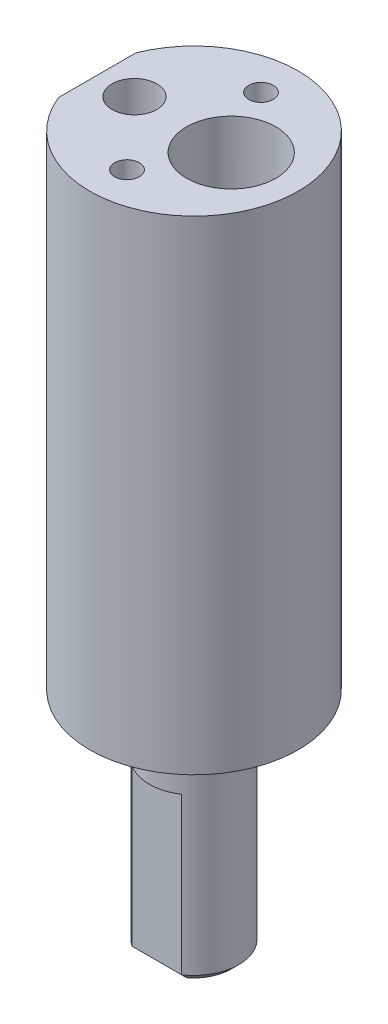
SolidWorks part; units mm, degrees
ref_plane "Front Plane" through (0, 0, 0) normal (0, 0, 1) x (1, 0, 0)
ref_plane "Top Plane" through (0, 0, 0) normal (0, 1, 0) x (1, 0, 0)
ref_plane "Right Plane" through (0, 0, 0) normal (1, 0, 0) x (0, 0, -1)
sketch "Sketch2" plane through (0, 0, 0) normal (0, 1, 0) x (1, 0, 0)
  line L0 (3.3166, -5) -> (-3.3166, -5)
  arc A0 (3.3166, -5) -> (-3.3166, -5) centre (0, 0) ccw
  dimension "D1" = 12
  dimension "D2" = 5
extrude "Boss-Extrude2" add sketch "Sketch2" along normal blind 22 contours A0 L0
sketch "Sketch6" plane through (0, 22, 0) normal (0, 1, 0) x (1, 0, 0)
  circle A0 centre (0, 0) radius 6
  dimension "D1" = 12
extrude "Boss-Extrude3" add sketch "Sketch6" along normal blind 8
sketch "Sketch7" plane through (0, 30, 0) normal (0, 1, 0) x (1, 0, 0)
  line L0 (-13, 5.1962) -> (-13, -5.1962)
  arc A0 (-13, -5.1962) -> (-13, 5.1962) centre (0, 0) ccw
  dimension "D1" = 28
  dimension "D2" = 13
extrude "Boss-Extrude4" add sketch "Sketch7" along normal blind 65
sketch "Sketch8" plane through (0, 95, 0) normal (0, 1, 0) x (1, 0, 0)
  line L0 (0, 0) -> (-13, 0) construction
  line L1 (-13, 5.1962) -> (-13, -5.1962) construction
  circle A0 centre (-8, 0) radius 3
  dimension "D2" = 6
  dimension "D1" = 8
extrude "Cut-Extrude5" cut sketch "Sketch8" against normal blind 65 contours A0
sketch "Sketch9" plane through (0, 95, 0) normal (0, 1, 0) x (1, 0, 0)
  circle A0 centre (5, 0) radius 6
  dimension "D2" = 12
  dimension "D1" = 5
extrude "Cut-Extrude6" cut sketch "Sketch9" against normal blind 52 contours A0
sketch "Sketch11" plane through (0, 95, 0) normal (0, 1, 0) x (1, 0, 0)
  line L0 (0, 14) -> (0, -14) construction
  arc A0 (-13, -5.1962) -> (-13, 5.1962) centre (0, 0) ccw construction
  point P6 (0, 9)
  point P7 (0, -9)
  point P8 (0, 9)
  dimension "D1" = 9
  dimension "D2" = 9
hole_wizard "M4 Tapped Hole1" positions "3DSketch1" profile "Sketch12" tap size "M4" standard "ISO"
sketch3d "3DSketch1"
  point P0 (0, 95, -9)
  point P3 (0, 95, 9)
sketch "Sketch12" plane through (0, 95, -9) normal (1, 0, 0) x (0, 0, 1)
  line L0 (0, 0) -> (0, 14.9914)
  line L1 (0, 14.9914) -> (1.65, 14)
  line L2 (1.65, 14) -> (1.65, 0)
  line L5 (1.65, 0) -> (0, 0)
  line L10 (0, 14.9914) -> (-1.65, 14) construction
  line L11 (0, -6.35) -> (0, 107.95) construction
  dimension "Tap Drill Dia." = 3.3
  dimension "Tap Drill Depth" = 14
  dimension "Drill Angle" = 118
cosmetic thread "Hole Thread1" parameters "D1"=13, "D2"=4
cosmetic thread "Hole Thread2" parameters "D1"=13, "D2"=4
sketch "Sketch13" plane through (-13, 0, 0) normal (-1, 0, 0) x (0, 0, 1)
  line L0 (0, 30) -> (0, 99.5149) construction
  line L1 (1.9111, 30) -> (-1.9111, 30) construction
  circle A0 centre (0, 34) radius 1.5
  circle A1 centre (0, 63) radius 2.5
  dimension "D1" = 5
  dimension "D2" = 3
  dimension "D3" = 32
  dimension "D4" = 29
extrude "Cut-Extrude7" cut sketch "Sketch13" against normal blind 5
sketch "Sketch14" plane through (-13, 0, 0) normal (-1, 0, 0) x (0, 0, 1)
  line L0 (0, 95) -> (0, 30) construction
  line L1 (-14, 95) -> (14, 95) construction
  line L2 (-5.1962, 30) -> (5.1962, 30) construction
  circle A0 centre (0, 85) radius 1
  circle A1 centre (0, 43) radius 1
  dimension "D3" = 2
  dimension "D1" = 10
  dimension "D2" = 52
extrude "Cut-Extrude8" cut sketch "Sketch14" against normal blind 15
chamfer "Chamfer1" distance 1 angle 45 2 edges at (0, 0, 5) (0, 0, -6)
